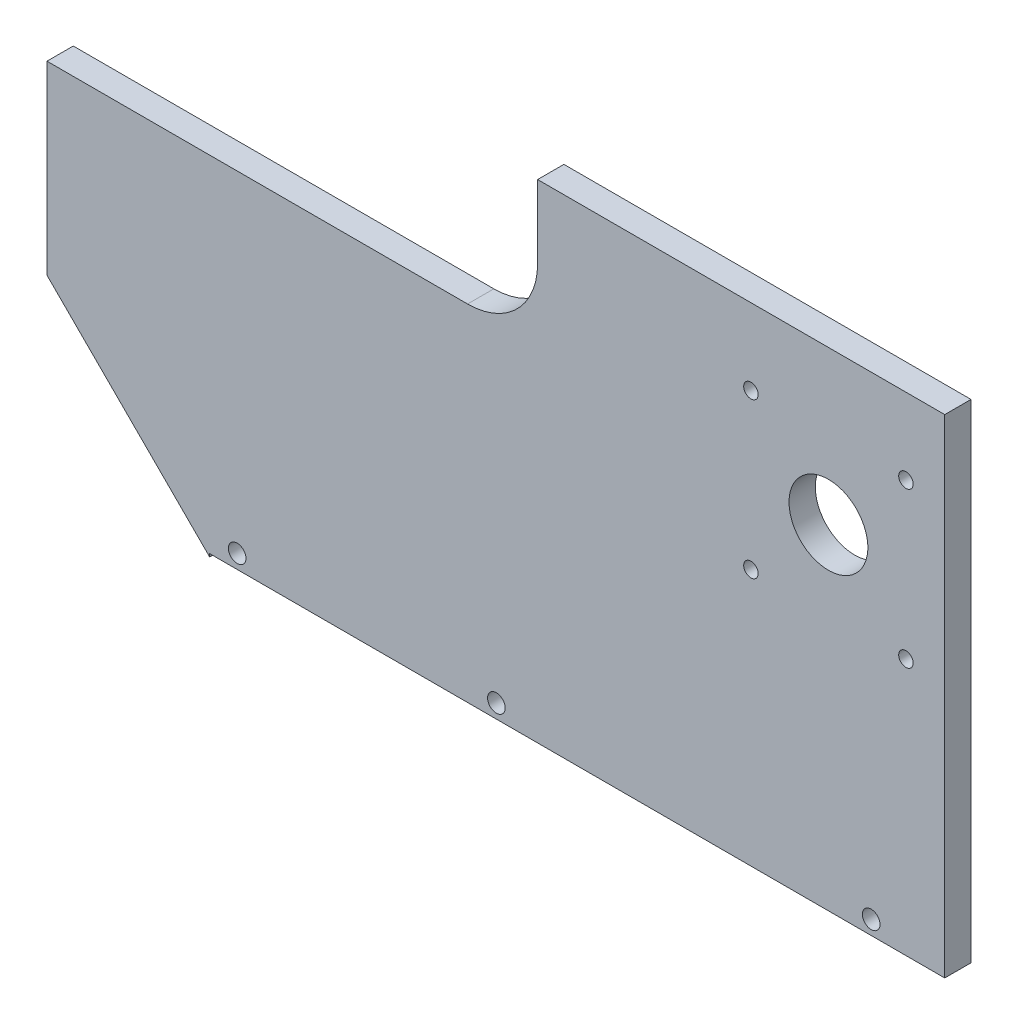
SolidWorks part; units mm, degrees
ref_plane "Front Plane" through (0, 0, 0) normal (0, 0, 1) x (1, 0, 0)
ref_plane "Top Plane" through (0, 0, 0) normal (0, 1, 0) x (1, 0, 0)
ref_plane "Right Plane" through (0, 0, 0) normal (1, 0, 0) x (0, 0, -1)
sketch "Sketch1" plane through (0, 0, 0) normal (0, 0, 1) x (1, 0, 0)
  line L0 (-138.2594, 48.9915) -> (32.2106, -121.4785)
  line L1 (32.2106, -121.4785) -> (222.7106, -121.4785)
  line L2 (-138.2594, 149.5088) -> (-138.2594, 48.9915)
  line L3 (-138.2594, 149.5088) -> (222.7106, 149.5088)
  line L4 (222.7106, -121.4785) -> (222.7106, 149.5088)
  circle A0 centre (180.538, 76.832) radius 14.2875
  circle A2 centre (180.538, 76.832) radius 69.85 construction
  circle A3 centre (180.538, 76.832) radius 318.7974 construction
  point P0 (0, 0)
  point P2 (180.538, 76.832)
  dimension "D4" = 198.3105
  dimension "D1" = 45
  dimension "D2" = 270.9874
  dimension "D5" = 245.11
extrude "Boss-Extrude1" add sketch "Sketch1" along normal blind 9.525
sketch "Sketch2" plane through (0, 0, 9.525) normal (0, 0, 1) x (1, 0, 0)
  line L0 (32.2106, -121.4785) -> (222.7106, -121.4785) construction
  line L1 (241.7606, -121.4785) -> (-43.8123, -121.4785)
  line L2 (241.7606, -121.4785) -> (241.7606, -44.3895)
  line L3 (241.7606, -44.3895) -> (-43.8123, -44.3895)
  line L4 (-43.8123, -121.4785) -> (-43.8123, -44.3895)
extrude "Cut-Extrude1" cut sketch "Sketch2" against normal through all contours L3 L4 L1 L2
sketch "Sketch4" plane through (0, 0, 9.525) normal (0, 0, 1) x (1, 0, 0)
  line L1 (-138.2594, 149.5088) -> (-138.2594, 48.9915) construction
  line L3 (-138.2594, 149.5088) -> (75.1006, 149.5088)
  line L4 (-138.2594, 149.5088) -> (-138.2594, 80.7415)
  line L5 (-138.2594, 80.7415) -> (75.1006, 80.7415)
  line L6 (75.1006, 149.5088) -> (75.1006, 80.7415)
extrude "Cut-Extrude2" cut sketch "Sketch4" against normal through all contours L5 L6 L3 L4
fillet "Fillet2" radius 25.4 2 edges at (-138.2594, 80.7415, 4.7625) (75.1006, 80.7415, 4.7625)
sketch "Sketch16" plane through (222.7106, 0, 0) normal (1, 0, 0) x (0, 0, -1)
  line L0 (0, -44.3895) -> (0, 149.5088) construction
  line L1 (-9.525, 149.5088) -> (0, 149.5088)
  line L2 (-9.525, 149.5088) -> (-9.525, 145.2215)
  line L3 (-9.525, 145.2215) -> (0, 145.2215)
  line L4 (0, 149.5088) -> (0, 145.2215)
extrude "Cut-Extrude3" cut sketch "Sketch16" against normal through all
sketch "Sketch17" plane through (0, 0, 0) normal (0, 0, -1) x (-1, 0, 0)
  line L0 (-222.7106, -44.3895) -> (-222.7106, 145.2215) construction
  line L1 (-75.1006, 145.2215) -> (-222.7106, 145.2215)
  line L2 (-75.1006, 145.2215) -> (-75.1006, 132.5215)
  line L3 (-75.1006, 132.5215) -> (-222.7106, 132.5215)
  line L4 (-222.7106, 145.2215) -> (-222.7106, 132.5215)
  dimension "D1" = 12.7
extrude "Cut-Extrude4" cut sketch "Sketch17" against normal through all
hole_wizard "Tap Drill for M6x0.75 Tap1" positions "Sketch19" profile "Sketch18" hole size "M6x0.75" standard "Lanco STD" end condition through all
sketch "Sketch19" plane through (0, 0, 9.525) normal (0, 0, 1) x (1, 0, 0)
  point P0 (208.638, 104.932)
  point P3 (152.438, 104.932)
  point P6 (152.438, 48.732)
  point P9 (208.638, 48.732)
sketch "Sketch18" plane through (208.638, 104.932, 9.525) normal (1, 0, 0) x (0, -1, 0)
  line L0 (0, 0) -> (0, 9.525)
  line L1 (0, 9.525) -> (2.625, 9.525)
  line L2 (2.625, 9.525) -> (2.625, 0)
  line L5 (2.625, 0) -> (0, 0)
  line L11 (0, -6.35) -> (0, 107.95) construction
  dimension "Thru Hole Dia." = 5.25
  dimension "Thru Hole Depth" = 9.525
hole_wizard "Ø6.4 (6.4) Diameter Hole1" positions "Sketch21" profile "Sketch20" hole size "Ø6.4" standard "ANSI Metric" end condition through all
sketch "Sketch21" plane through (0, 0, 9.525) normal (0, 0, 1) x (1, 0, 0)
  point P0 (196.0406, -39.3145)
  point P2 (60.1506, -39.3145)
  point P4 (-33.8294, -39.3145)
sketch "Sketch20" plane through (196.0406, -39.3145, 9.525) normal (1, 0, 0) x (0, -1, 0)
  line L0 (0, 0) -> (0, 9.525)
  line L1 (0, 9.525) -> (3.2, 9.525)
  line L2 (3.2, 9.525) -> (3.2, 0)
  line L5 (3.2, 0) -> (0, 0)
  line L11 (0, -6.35) -> (0, 107.95) construction
  dimension "Thru Hole Dia." = 6.4
  dimension "Thru Hole Depth" = 9.525
sketch "Sketch22" plane through (0, 0, 9.525) normal (0, 0, 1) x (1, 0, 0)
  line L0 (-102.7904, 145.0855) -> (-102.7904, -100.3395)
  line L1 (222.7106, -44.3895) -> (222.7106, 132.5215) construction
  line L2 (-102.7904, 145.0855) -> (-209.6758, 145.0855)
  line L3 (-209.6758, 145.0855) -> (-209.6758, -95.574)
  line L4 (-209.6758, -95.574) -> (-102.7904, -100.3395)
  dimension "D1" = 325.501
extrude "Cut-Extrude5" cut sketch "Sketch22" against normal through all
